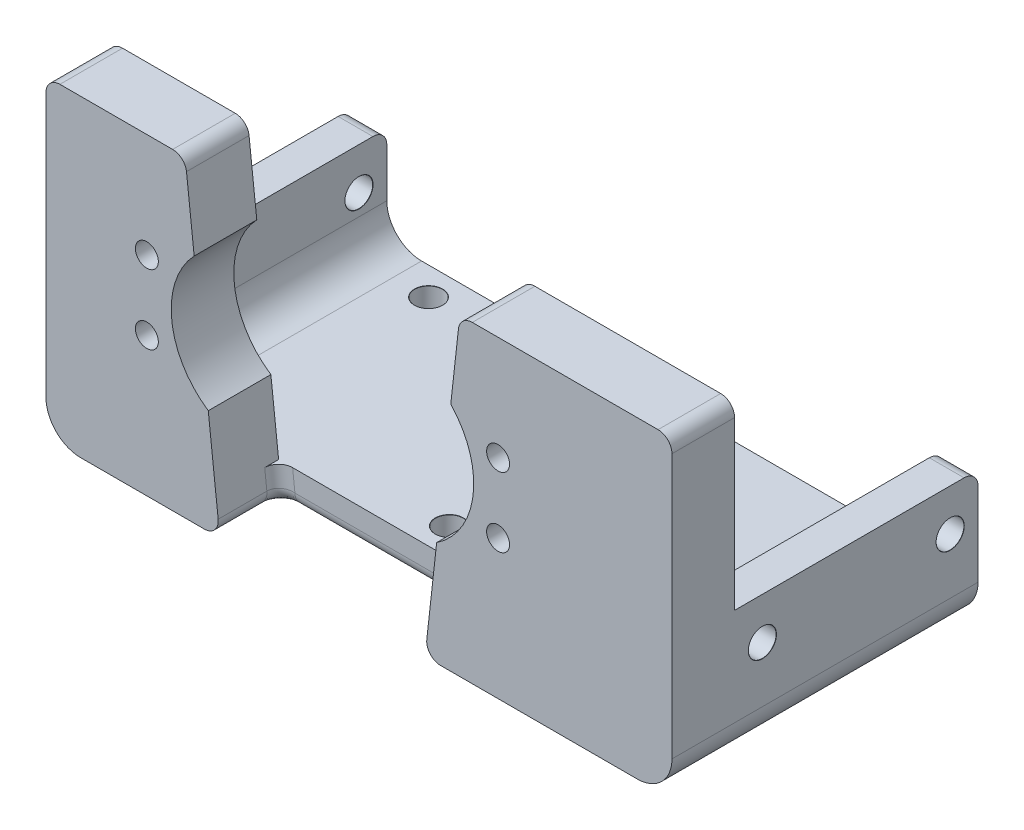
SolidWorks part; units mm, degrees
ref_plane "Front Plane" through (0, 0, 0) normal (0, 0, 1) x (1, 0, 0)
ref_plane "Top Plane" through (0, 0, 0) normal (0, 1, 0) x (1, 0, 0)
ref_plane "Right Plane" through (0, 0, 0) normal (1, 0, 0) x (0, 0, -1)
sketch "Sketch1" plane through (0, 0, 0) normal (0, 0, 1) x (1, 0, 0)
  line L0 (-45, 7) -> (-45, -12)
  line L1 (-40, 7) -> (40, 7) construction
  line L2 (-40, 7) -> (-40, -7)
  line L3 (-40, -7) -> (40, -7)
  line L4 (40, 7) -> (40, -7)
  line L5 (-40, 7) -> (40, -7) construction
  line L6 (-40, -7) -> (40, 7) construction
  line L7 (-45, -12) -> (45, -12)
  line L8 (45, 7) -> (45, -12)
  line L9 (-45, 7) -> (-40, 7)
  line L10 (40, 7) -> (45, 7)
  point P0 (0, 0)
  dimension "D1" = 80
  dimension "D2" = 14
  dimension "D3" = 5
extrude "Boss-Extrude1" add sketch "Sketch1" along normal blind 35
sketch "Sketch2" plane through (0, 0, 35) normal (0, 0, 1) x (1, 0, 0)
  line L0 (-45, -12) -> (-45, 33)
  line L1 (-45, 33) -> (-25, 33)
  line L2 (-25, 33) -> (-20, -12)
  line L3 (-45, -12) -> (45, -12) construction
  line L4 (-20, -12) -> (-45, -12)
  line L5 (40, 33) -> (-40, 33) construction
  line L16 (-24.45, 23) -> (-32, 23)
  line L17 (-33, 22) -> (-33, 19)
  line L18 (-33, 19) -> (-32.2321, 19)
  line L19 (-32.2321, 17) -> (-33, 17)
  line L20 (-33, 17) -> (-33, 9)
  line L21 (-33, 9) -> (-32.2321, 9)
  line L22 (-32.2321, 7) -> (-33, 7)
  line L23 (-33, 7) -> (-33, 4)
  line L24 (-32, 3) -> (-24.45, 3)
  line L25 (-25.45, 4) -> (-25.45, 22)
  line L26 (-24.45, 23) -> (-32, 23) construction
  line L27 (-33, 22) -> (-33, 19) construction
  line L28 (-33, 19) -> (-32.2321, 19) construction
  line L29 (-32.2321, 17) -> (-33, 17) construction
  line L30 (-33, 17) -> (-33, 9) construction
  line L31 (-33, 9) -> (-32.2321, 9) construction
  line L32 (-32.2321, 7) -> (-33, 7) construction
  line L33 (-33, 7) -> (-33, 4) construction
  line L34 (-32, 3) -> (-24.45, 3) construction
  line L35 (-25.45, 4) -> (-25.45, 22) construction
  circle A0 centre (-15, 13) radius 12
  circle A1 centre (-30.5, 8) radius 1.65
  circle A2 centre (-30.5, 18) radius 1.65
  arc A6 (-32, 23) -> (-33, 22) centre (-32, 22) ccw
  arc A7 (-32.2321, 17) -> (-32.2321, 19) centre (-30.5, 18) ccw
  arc A8 (-32.2321, 7) -> (-32.2321, 9) centre (-30.5, 8) ccw
  arc A9 (-33, 4) -> (-32, 3) centre (-32, 4) ccw
  arc A10 (-25.45, 4) -> (-24.45, 3) centre (-24.45, 4) ccw
  arc A11 (-24.45, 23) -> (-25.45, 22) centre (-24.45, 22) ccw
  arc A12 (-32, 23) -> (-33, 22) centre (-32, 22) ccw construction
  arc A13 (-32.2321, 17) -> (-32.2321, 19) centre (-30.5, 18) ccw construction
  arc A14 (-32.2321, 7) -> (-32.2321, 9) centre (-30.5, 8) ccw construction
  arc A15 (-33, 4) -> (-32, 3) centre (-32, 4) ccw construction
  arc A16 (-25.45, 4) -> (-24.45, 3) centre (-24.45, 4) ccw
  arc A17 (-24.45, 23) -> (-25.45, 22) centre (-24.45, 22) ccw construction
  dimension "D4" = 24
  dimension "D5" = 3.3
  dimension "D1" = 25
  dimension "D2" = 20
  dimension "D3" = 0
extrude "Boss-Extrude2" add sketch "Sketch2" along normal blind 9
ref_plane "Plane1" through (-5.25, 13.7849, -116.6479) normal (-1, 0, 0) x (0, 0, -1)
mirror "Mirror2" about plane through (-5.25, 13.7849, -116.6479) normal (-1, 0, 0) of "Boss-Extrude2"
sketch "Sketch4" plane through (34.5, 0, 0) normal (1, 0, 0) x (0, 0, -1)
  line L5 (-35, -7) -> (-35, 33)
  line L6 (-35, 33) -> (-44, 33)
  line L7 (-44, 33) -> (-44, -12)
  line L8 (-44, -12) -> (-35, -12)
  line L9 (-35, -12) -> (-35, -7)
  line L10 (-35, -7) -> (-35, 33)
  line L11 (-35, 33) -> (-44, 33)
  line L12 (-44, 33) -> (-44, -12)
  line L13 (-44, -12) -> (-35, -12)
  line L14 (-35, -12) -> (-35, -7)
  dimension "D1" = 0
extrude "Boss-Extrude3" add sketch "Sketch4" along normal up to surface (10.5 mm away) up to face at (45, -2.5, 17.5)
sketch "Sketch5" plane through (0, 0, 35) normal (0, 0, -1) x (-1, 0, 0)
  circle A1 centre (-4.5, 13) radius 19.5
  dimension "D1" = 39
extrude "Cut-Extrude1" cut sketch "Sketch5" against normal blind 3
fillet "Fillet1" radius 5 4 edges at (45, -12, 22) (-45, -12, 22) (40, -7, 17.5) (-40, -7, 17.5)
fillet "Fillet2" radius 2 11 edges at (-5.25, -12, 35) (-45, 33, 39.5) (-25, 33, 39.5) (45, 33, 39.5) (-42.5, 7, 0) (42.5, 7, 0) (14.5, 33, 39.5) (9.7778, -9.5, 35) (-20.2778, -9.5, 35) (-20, -12, 39.5) (9.5, -12, 39.5)
hole_wizard "Ø4.0mm Dowel Hole2" positions "3DSketch1" profile "Sketch6" hole size "Ø4.0" standard "ANSI Metric" end condition up to next
sketch3d "3DSketch1"
  line L0 (-45, -7, 0) -> (-45, -7, 44) construction
  line L1 (-45, -7, 0) -> (-45, -7, 44)
  line L2 (-40, -12, 4) -> (40, -12, 4) construction
  line L3 (-40, -12, 44) -> (-40, -12, 0) construction
  line L4 (40, -12, 0) -> (40, -12, 44) construction
  line L7 (-40, -12, 0) -> (40, -12, 0) construction
  arc A0 (45, -7, 0) -> (40, -12, 0) centre (40, -7, 0) ccw construction
  arc A1 (45, -7, 0) -> (40, -12, 0) centre (40, -7, 0) ccw
  point P0 (0, -12, 4)
  point P2 (30, -12, 4)
  point P4 (-30, -12, 4)
  point P12 (40, -7, -5)
  point P13 (40, -7, -5)
  point P27 (30, -12, 4)
  point P29 (30, -12, 4)
  point P34 (-30, -12, 4)
  point P37 (0, 0, 0)
  point P38 (-30, -12, 4)
  dimension "D1" = 4
  dimension "D2" = 10
  dimension "D3" = 10
sketch "Sketch6" plane through (0, -12, 4) normal (1, 0, 0) x (0, 0, -1)
  line L0 (0, 0) -> (0, 5)
  line L1 (0, 5) -> (2.025, 5)
  line L2 (2, 4.975) -> (2, 0.025)
  line L3 (2, 0.025) -> (2.025, 0)
  line L5 (2.025, 0) -> (0, 0)
  line L6 (-2, 0.025) -> (-2.025, 0) construction
  line L7 (2.025, 5) -> (2, 4.975)
  line L8 (-2.025, 5) -> (-2, 4.975) construction
  line L11 (0, -6.35) -> (0, 107.95) construction
  dimension "Thru Hole Dia." = 4
  dimension "Thru Hole Depth" = 5
  dimension "Near C'Sink Dia." = 4.05
  dimension "Near C'Sink Angle" = 90
  dimension "Far C'Sink Dia." = 4.05
  dimension "Far C'Sink Angle" = 90
hole_wizard "Ø4.0mm Dowel Hole3" positions "Sketch8" profile "Sketch9" hole size "Ø4.0" standard "ANSI Metric" end condition up to next
sketch "Sketch8" plane through (45, 0, 0) normal (1, 0, 0) x (0, 0, -1)
  line L0 (0, -7) -> (0, 5) construction
  line L1 (-35, 7) -> (-2, 7) construction
  point P0 (-4, 1)
  dimension "D1" = 4
  dimension "D2" = 6
sketch "Sketch9" plane through (45, 1, 4) normal (0, 1, 0) x (0, 0, -1)
  line L0 (0, 0) -> (0, 5)
  line L1 (0, 5) -> (2.025, 5)
  line L2 (2, 4.975) -> (2, 0.025)
  line L3 (2, 0.025) -> (2.025, 0)
  line L5 (2.025, 0) -> (0, 0)
  line L6 (-2, 0.025) -> (-2.025, 0) construction
  line L7 (2.025, 5) -> (2, 4.975)
  line L8 (-2.025, 5) -> (-2, 4.975) construction
  line L11 (0, -6.35) -> (0, 107.95) construction
  dimension "Thru Hole Dia." = 4
  dimension "Thru Hole Depth" = 5
  dimension "Near C'Sink Dia." = 4.05
  dimension "Near C'Sink Angle" = 90
  dimension "Far C'Sink Dia." = 4.05
  dimension "Far C'Sink Angle" = 90
mirror "Mirror3" about plane through (0, 0, 0) normal (1, 0, 0) of "Ø4.0mm Dowel Hole3"
ref_plane "Plane2" through (0, 0, 17.5) normal (0, 0, -1) x (-1, 0, 0)
mirror "Mirror4" about plane through (0, 0, 17.5) normal (0, 0, -1) of "Ø4.0mm Dowel Hole2", "Ø4.0mm Dowel Hole3", "Mirror3"
